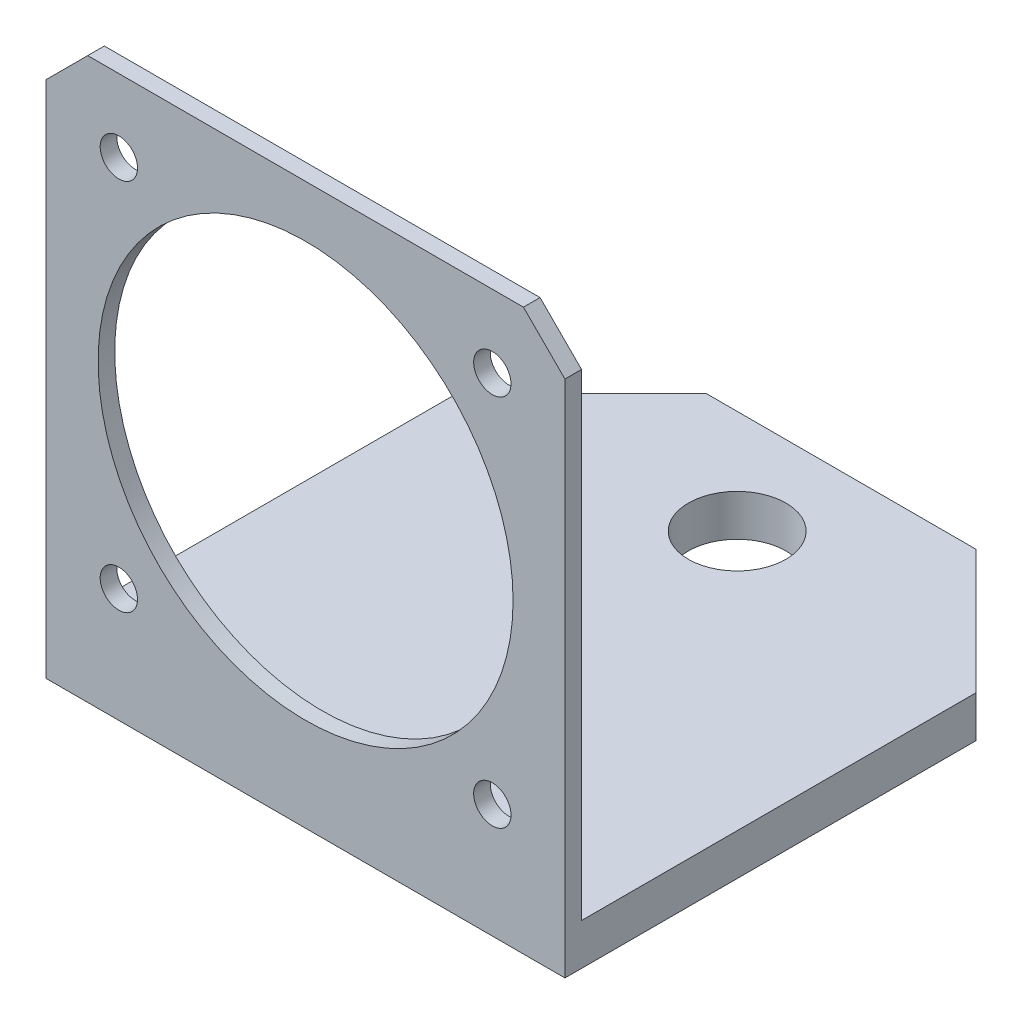
SolidWorks part; units mm, degrees
ref_plane "Front Plane" through (0, 0, 0) normal (0, 0, 1) x (1, 0, 0)
ref_plane "Top Plane" through (0, 0, 0) normal (0, 1, 0) x (1, 0, 0)
ref_plane "Right Plane" through (0, 0, 0) normal (1, 0, 0) x (0, 0, -1)
sketch "Sketch1" plane through (0, 0, 0) normal (0, 0, 1) x (1, 0, 0)
  line L1 (-15.875, -15.875) -> (15.875, -15.875)
  line L2 (-15.875, -15.875) -> (-15.875, 15.875)
  line L3 (-15.875, 15.875) -> (15.875, 15.875)
  line L4 (15.875, -15.875) -> (15.875, 15.875)
  line L5 (-15.875, -15.875) -> (15.875, 15.875) construction
  line L6 (-15.875, 15.875) -> (15.875, -15.875) construction
  circle A0 centre (-11.43, 11.43) radius 1.143
  circle A1 centre (11.43, 11.43) radius 1.143
  circle A2 centre (-11.43, -11.43) radius 1.143
  circle A3 centre (11.43, -11.43) radius 1.143
  circle A4 centre (0, 0) radius 12.7
  point P0 (0, 0)
  dimension "D3" = 2.286
  dimension "D6" = 25.4
  dimension "D1" = 31.75
  dimension "D2" = 31.75
  dimension "D4" = 22.86
  dimension "D5" = 22.86
extrude "Boss-Extrude1" add sketch "Sketch1" along normal blind 1.016
chamfer "Chamfer1" distance 2.54 angle 45 2 edges at (-15.875, 15.875, 0.508) (15.875, 15.875, 0.508)
sketch "Sketch2" plane through (0, -15.875, 0) normal (0, -1, 0) x (1, 0, 0)
  line L0 (-15.875, 1.016) -> (-15.875, 0) construction
  line L1 (15.875, 1.016) -> (-15.875, 1.016)
  line L2 (15.875, 1.016) -> (15.875, -31.75)
  line L3 (15.875, -31.75) -> (-15.875, -31.75)
  line L4 (-15.875, 1.016) -> (-15.875, -31.75)
  line L5 (-15.875, 0) -> (15.875, 0) construction
  dimension "D1" = 31.75
extrude "Boss-Extrude2" add sketch "Sketch2" along normal blind 2.54
sketch "Sketch3" plane through (0, -15.875, 0) normal (0, 1, 0) x (1, 0, 0)
  circle A0 centre (0, 25.4) radius 2.9845
  dimension "D1" = 5.969
  dimension "D2" = 25.4
extrude "Cut-Extrude1" cut sketch "Sketch3" against normal through all
chamfer "Chamfer2" distance 7.62 angle 45 2 edges at (15.875, -17.145, -31.75) (-15.875, -17.145, -31.75)
